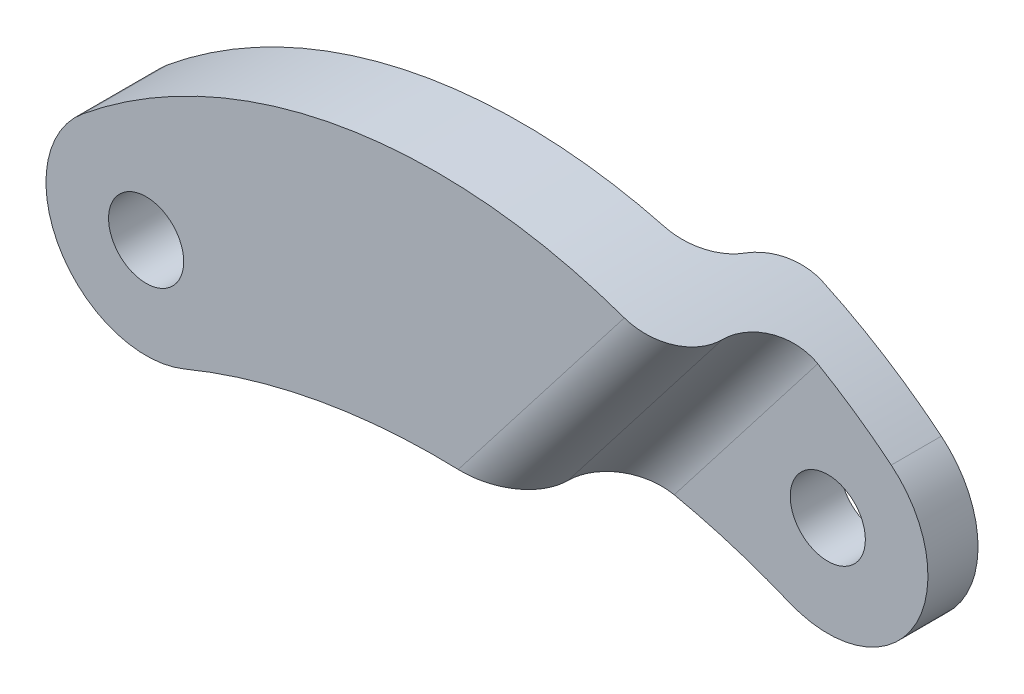
SolidWorks part; units mm, degrees
ref_plane "Front" through (0, 0, 0) normal (0, 0, 1) x (1, 0, 0)
ref_plane "Top" through (0, 0, 0) normal (0, 1, 0) x (1, 0, 0)
ref_plane "Right" through (0, 0, 0) normal (1, 0, 0) x (0, 0, -1)
sketch "Sketch1" plane through (0, 0, 0) normal (0, 0, 1) x (1, 0, 0)
  line L0 (0, 0) -> (11.61, 0) construction
  line L1 (0, 2) -> (11.61, 2)
  line L2 (0, -2) -> (11.61, -2)
  circle A0 centre (0, 0) radius 0.75
  circle A1 centre (11.61, 0) radius 0.75
  arc A2 (0, 2) -> (0, -2) centre (0, 0) ccw
  arc A3 (11.61, -2) -> (11.61, 2) centre (11.61, 0) ccw
  point P5 (5.805, 0)
  dimension "D1" = 1.5
  dimension "D3" = 2
  dimension "D2" = 11.61
extrude "Boss-Extrude1" add sketch "Sketch1" along normal mid plane 1
sketch "Sketch2" plane through (0, 0, 0.5) normal (0, 0, 1) x (1, 0, 0)
  line L0 (-1.2675, 1.5471) -> (12.8775, 1.5471)
  arc A0 (-1.2675, 1.5471) -> (12.8775, 1.5471) centre (5.805, -7.0858) cw
  arc A1 (0, 2) -> (0, -2) centre (0, 0) ccw construction
  arc A2 (11.61, -2) -> (11.61, 2) centre (11.61, 0) ccw construction
extrude "Boss-Extrude2" add sketch "Sketch2" against normal up to vertex (1 mm away) up to point (0, 2, -0.5)
sketch "Sketch3" plane through (0, 0, 0.5) normal (0, 0, 1) x (1, 0, 0)
  line L0 (5.805, -2) -> (5.805, -14.014) construction
  line L1 (0, -2) -> (11.61, -2) construction
  line L2 (11.61, -2) -> (0, -2)
  arc A0 (0.7654, -1.8477) -> (10.8446, -1.8477) centre (5.805, -14.014) cw
  arc A1 (0.7654, -1.8477) -> (0, -2) centre (0, 0) cw
  arc A2 (-1.2675, 1.5471) -> (0, -2) centre (0, 0) ccw construction
  arc A3 (10.8446, -1.8477) -> (11.61, -2) centre (11.61, 0) ccw
  arc A4 (11.61, -2) -> (12.8775, 1.5471) centre (11.61, 0) ccw construction
extrude "Cut-Extrude1" cut sketch "Sketch3" against normal through all
sketch "Sketch4" plane through (0, 0, 0.5) normal (0, 0, 1) x (1, 0, 0)
  line L0 (10.5085, 3.0347) -> (7.4247, -0.9453)
  arc A0 (12.8775, 1.5471) -> (-1.2675, 1.5471) centre (5.805, -7.0858) ccw construction
  arc A1 (10.8446, -1.8477) -> (0.7654, -1.8477) centre (5.805, -14.014) ccw construction
  circle A2 centre (0, 0) radius 0.75 construction
  circle A3 centre (0, 0) radius 0.75
  arc A6 (-1.2675, 1.5471) -> (0.7654, -1.8477) centre (0, 0) ccw
  arc A7 (10.8446, -1.8477) -> (0.7654, -1.8477) centre (5.805, -14.014) ccw
  arc A8 (10.8446, -1.8477) -> (12.8775, 1.5471) centre (11.61, 0) ccw
  arc A9 (12.8775, 1.5471) -> (-1.2675, 1.5471) centre (5.805, -7.0858) ccw
  arc A10 (-1.2675, 1.5471) -> (0.7654, -1.8477) centre (0, 0) ccw
  arc A11 (7.4247, -0.9453) -> (0.7654, -1.8477) centre (5.805, -14.014) ccw
  arc A13 (10.5085, 3.0347) -> (-1.2675, 1.5471) centre (5.805, -7.0858) ccw
  dimension "D1" = 0
extrude "Boss-Extrude3" add sketch "Sketch4" along normal blind 2
sketch "Sketch6" plane through (0, 0, 2.5) normal (0, 0, 1) x (1, 0, 0)
  line L0 (7.4247, -0.9453) -> (10.5085, 3.0347) construction
  line L1 (7.4247, -0.9453) -> (10.5085, 3.0347)
  line L2 (6.2318, -0.8522) -> (9.5481, 3.4278)
  arc A3 (10.5085, 3.0347) -> (-1.2675, 1.5471) centre (5.805, -7.0858) ccw
  arc A4 (-1.2675, 1.5471) -> (0.7654, -1.8477) centre (0, 0) ccw
  arc A5 (7.4247, -0.9453) -> (0.7654, -1.8477) centre (5.805, -14.014) ccw
  arc A6 (9.5481, 3.4278) -> (-1.2675, 1.5471) centre (5.805, -7.0858) ccw
  arc A7 (-1.2675, 1.5471) -> (0.7654, -1.8477) centre (0, 0) ccw
  arc A8 (6.2318, -0.8522) -> (0.7654, -1.8477) centre (5.805, -14.014) ccw
  dimension "D2" = 1
  dimension "D1" = 0
extrude "Cut-Extrude2" cut sketch "Sketch6" against normal blind 10 from offset 1.7 offset against normal yes
fillet "Fillet1" radius 1 2 edges at (8.9666, 1.0447, 2.5) (7.8899, 1.2878, -0.5)
fillet "Fillet2" radius 1 2 edges at (8.9666, 1.0447, 0.5) (7.8899, 1.2878, 0.8)
